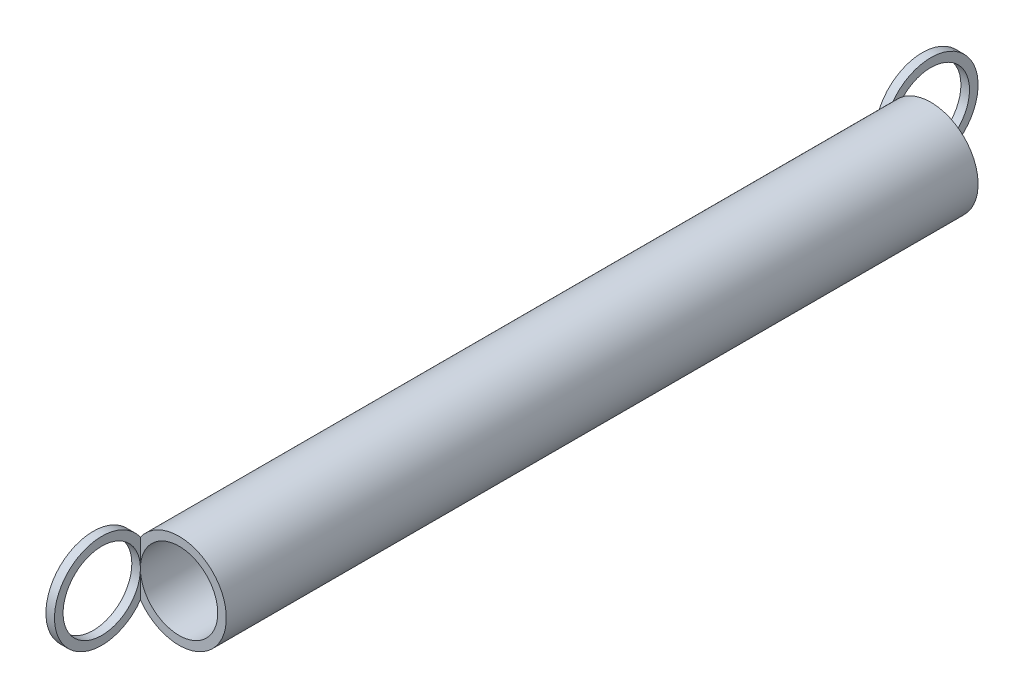
SolidWorks part; units mm, degrees
ref_plane "Front Plane" through (0, 0, 0) normal (0, 0, 1) x (1, 0, 0)
ref_plane "Top Plane" through (0, 0, 0) normal (0, 1, 0) x (1, 0, 0)
ref_plane "Right Plane" through (0, 0, 0) normal (1, 0, 0) x (0, 0, -1)
sketch "Sketch1" plane through (0, 0, 0) normal (0, 0, 1) x (1, 0, 0)
  circle A0 centre (0, 0) radius 2.2
  circle A1 centre (0, 0) radius 1.8
  dimension "D1" = 4.4
  dimension "D2" = 0.4
extrude "Boss-Extrude1" add sketch "Sketch1" along normal mid plane 35
ref_plane "Plane1" through (-1.8, 0, 0) normal (1, 0, 0) x (0, 0, -1)
sketch "Sketch2" plane through (-1.8, 0, 0) normal (1, 0, 0) x (0, 0, -1)
  line L0 (-17.5, 2.2) -> (-17.5, -2.2) construction
  line L1 (17.5, -2.2) -> (17.5, 2.2) construction
  circle A0 centre (-19.3, 0) radius 1.8
  circle A1 centre (-19.3, 0) radius 2.2
  circle A2 centre (19.3, 0) radius 1.8
  circle A3 centre (19.3, 0) radius 2.2
  point P6 (-19.3, 1.8)
  point P7 (-19.3, 2.2)
  point P8 (0, 0)
  point P12 (0, 0)
extrude "Boss-Extrude2" add sketch "Sketch2" against normal through all
